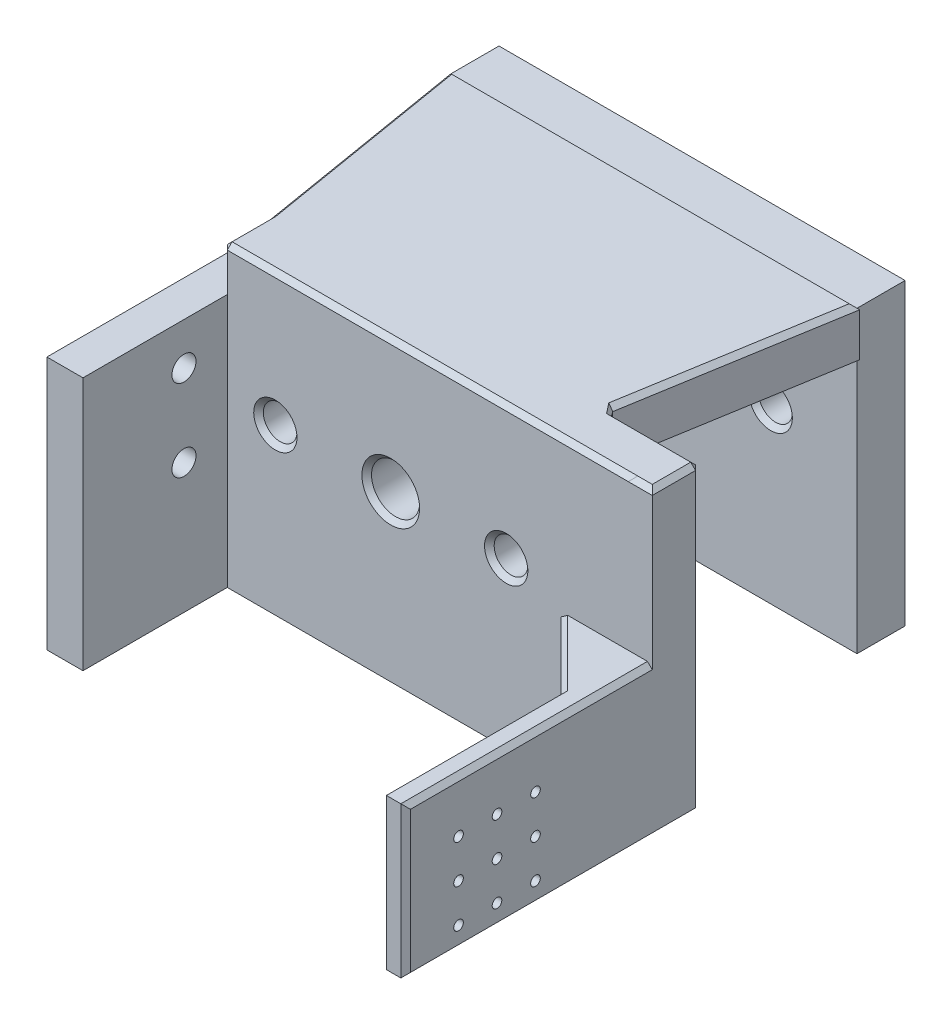
SolidWorks part; units mm, degrees
ref_plane "Front" through (0, 0, 0) normal (0, 0, 1) x (1, 0, 0)
ref_plane "Top" through (0, 0, 0) normal (0, 1, 0) x (1, 0, 0)
ref_plane "Right" through (0, 0, 0) normal (1, 0, 0) x (0, 0, -1)
sketch "Sketch1" plane through (0, 0, 0) normal (0, 0, 1) x (1, 0, 0)
  line L1 (0, 0) -> (70, 0)
  line L2 (0, 0) -> (0, 62.75)
  line L3 (0, 62.75) -> (70, 62.75)
  line L4 (70, 0) -> (70, 62.75)
  dimension "D1" = 70
  dimension "D2" = 62.75
extrude "Boss-Extrude1" add sketch "Sketch1" along normal blind 10
sketch "Sketch2" plane through (0, 0, 10) normal (0, 0, 1) x (1, 0, 0)
  line L1 (70, 62.75) -> (0, 62.75) construction
  line L2 (70, 0) -> (70, 62.75) construction
  circle A0 centre (35, 35.25) radius 5
  dimension "D1" = 27.5
  dimension "D3" = 10
  dimension "D2" = 35
extrude "Cut-Extrude1" cut sketch "Sketch2" against normal through all
sketch "Sketch3" plane through (0, 0, 10) normal (0, 0, 1) x (1, 0, 0)
  line L1 (35, 35.25) -> (92.1007, 35.25) construction
  circle A0 centre (11, 35.25) radius 3.5
  circle A1 centre (59, 35.25) radius 3.5
  circle A2 centre (35, 35.25) radius 5 construction
  dimension "D1" = 7
  dimension "D2" = 7
  dimension "D4" = 48
  dimension "D5" = 24
extrude "Cut-Extrude2" cut sketch "Sketch3" against normal through all
sketch "Sketch4" plane through (0, 62.75, 0) normal (0, 1, 0) x (1, 0, 0)
  line L0 (0, 0) -> (-7.5, 45)
  line L1 (-7.5, 45) -> (77.5, 45)
  line L2 (77.5, 45) -> (70, 0)
  line L3 (70, 0) -> (0, 0)
  line L4 (35, 0) -> (35, 91.9933) construction
  dimension "D1" = 45
  dimension "D2" = 42.5
  dimension "D3" = 42.5
extrude "Boss-Extrude2" add sketch "Sketch4" against normal blind 10
sketch "Sketch5" plane through (0, 0, -45) normal (0, 0, -1) x (-1, 0, 0)
  line L0 (-77.5, 52.75) -> (7.5, 52.75) construction
  line L1 (-52.5, 52.75) -> (-17.5, 52.75)
  line L2 (-52.5, 52.75) -> (-52.5, 59.25)
  line L3 (-52.5, 59.25) -> (-17.5, 59.25)
  line L4 (-17.5, 52.75) -> (-17.5, 59.25)
  line L5 (-77.5, 62.75) -> (7.5, 62.75) construction
  line L6 (7.5, 52.75) -> (7.5, 62.75) construction
  dimension "D1" = 35
  dimension "D2" = 25
  dimension "D3" = 3.5
extrude "Cut-Extrude3" cut sketch "Sketch5" against normal up to surface (45 mm away) up to face at (14.5, 35.25, 0)
chamfer "Chamfer1" distance 1 angle 45 6 edges at (14.5, 35.25, 10) (14.5, 35.25, 0) (62.5, 35.25, 10) (62.5, 35.25, 0) (40, 35.25, 10) (40, 35.25, 0)
chamfer "Chamfer2" distance 6 angle 45 2 edges at (17.5, 52.75, -22.5) (52.5, 52.75, -22.5)
sketch "Sketch6" plane through (70, 0, 0) normal (1, 0, 0) x (0, 0, -1)
  line L1 (-10, 62.75) -> (0, 62.75)
  line L2 (-10, 62.75) -> (-10, 0)
  line L3 (-10, 0) -> (0, 0)
  line L4 (0, 62.75) -> (0, 0)
extrude "Boss-Extrude3" add sketch "Sketch6" along normal blind 19.37
sketch "Sketch7" plane through (0, 0, 10) normal (0, 0, 1) x (1, 0, 0)
  line L0 (89.37, 62.75) -> (0, 62.75) construction
  line L1 (84.37, 62.75) -> (89.37, 62.75)
  line L2 (84.37, 62.75) -> (84.37, 0)
  line L3 (84.37, 0) -> (89.37, 0)
  line L4 (89.37, 62.75) -> (89.37, 0)
  line L5 (0, 0) -> (89.37, 0) construction
  line L6 (89.37, 62.75) -> (89.37, 0) construction
  dimension "D1" = 5
extrude "Boss-Extrude4" add sketch "Sketch7" along normal blind 51.28
sketch "Sketch8" plane through (89.37, 0, 0) normal (1, 0, 0) x (0, 0, -1)
  line L0 (-61.28, 0) -> (-61.28, 62.75) construction
  line L1 (-61.28, 0) -> (0, 0) construction
  line L2 (-61.28, 20.5) -> (0, 20.5) construction
  line L3 (0, 0) -> (0, 62.75) construction
  line L4 (-50.28, 33.1269) -> (-50.28, -8.1623) construction
  circle A0 centre (-50.28, 20.5) radius 1
  circle A1 centre (-42.28, 20.5) radius 1
  circle A2 centre (-34.28, 20.5) radius 1
  circle A3 centre (-42.28, 20.5) radius 1
  circle A4 centre (-34.28, 20.5) radius 1
  circle A5 centre (-42.28, 12.5) radius 1
  circle A6 centre (-34.28, 12.5) radius 1
  circle A7 centre (-42.28, 4.5) radius 1
  circle A8 centre (-34.28, 4.5) radius 1
  circle A9 centre (-50.28, 12.5) radius 1
  circle A10 centre (-50.28, 4.5) radius 1
  dimension "D1" = 2
  dimension "D5" = 8
  dimension "D6" = 3
  dimension "D2" = 11
  dimension "D3" = 20.5
  dimension "D7" = 3
  dimension "D8" = 8
  dimension "D9" = 16
  dimension "D4" = 3
extrude "Cut-Extrude4" cut sketch "Sketch8" against normal up to next contours A2 | A1 | A9 | A5 | A6 | A8 | A7 | A0 | A10 region at (89.37, 20.5, 42.28) region at (89.37, 20.5, 34.28) region at (89.37, 12.5, 42.28) region at (89.37, 12.5, 34.28) region at (89.37, 4.5, 42.28) region at (89.37, 4.5, 34.28) region at (89.37, 12.5, 50.28)
chamfer "Chamfer3" distance 1 angle 45 16 edges at (70, 57.75, 0) (0, 26.375, 0) (89.37, 31.375, 0) (89.37, 31.375, 61.28) (89.37, 62.75, 30.64) (79.685, 62.75, 0) (73.75, 62.75, -22.5) (35, 62.75, -45) (-3.75, 62.75, -22.5) (0, 62.75, 5) (84.37, 31.375, 61.28) (84.37, 0, 35.64) (84.37, 62.75, 35.64) (42.185, 62.75, 10) (42.185, 0, 10) (0, 31.375, 10) first distance on face at (73.75, 57.75, -22.5) first distance on face at (0, 35.65, 4) first distance on face at (89.37, 12.5, 33.28) first distance on face at (54.1644, 62.75, 5.84) first distance on face at (35, 57.25, -45) first distance on face at (-3.75, 57.75, -22.5) first distance on face at (84.37, 12.5, 33.28) first distance on face at (57.9133, 0, 23.76)
sketch "Sketch9" plane through (84.37, 0, 0) normal (-1, 0, 0) x (0, 0, 1)
  line L0 (10, 61.75) -> (10, 1) construction
  line L1 (61.28, 62.75) -> (10, 62.75)
  line L2 (61.28, 62.75) -> (61.28, 31.375)
  line L3 (61.28, 31.375) -> (10, 31.375)
  line L4 (10, 62.75) -> (10, 31.375)
extrude "Cut-Extrude5" cut sketch "Sketch9" against normal up to next
chamfer "Chamfer4" distance 1 angle 45 1 edges at (86.87, 62.75, 10)
chamfer "Chamfer5" distance 1 angle 45 2 edges at (84.37, 31.375, 35.14) (89.37, 31.375, 35.14)
sketch "Sketch11" plane through (0, 0, 0) normal (0, 0, -1) x (-1, 0, 0)
  line L0 (-1, 0) -> (-88.37, 0) construction
  line L1 (-81.87, 3) -> (-76.87, 3)
  line L2 (-81.87, 3) -> (-81.87, 23)
  line L3 (-81.87, 23) -> (-76.87, 23)
  line L4 (-76.87, 3) -> (-76.87, 23)
  line L5 (-88.37, 61.75) -> (-88.37, 0) construction
  line L7 (-88.37, 3) -> (-46.6895, 3) construction
  dimension "D1" = 6.5
  dimension "D2" = 20
  dimension "D3" = 5
  dimension "D4" = 3
extrude "Cut-Extrude6" cut sketch "Sketch11" against normal blind 10
sketch "Sketch12" plane through (0, 31.375, 0) normal (0, 1, 0) x (1, 0, 0)
  line L0 (85.37, -25) -> (70.37, -10)
  line L1 (85.37, -10) -> (85.37, -61.28) construction
  line L2 (84.37, -10) -> (1, -10) construction
  line L3 (70.37, -10) -> (85.37, -10)
  line L4 (85.37, -10) -> (85.37, -25)
  dimension "D1" = 45
  dimension "D2" = 15
extrude "Boss-Extrude5" add sketch "Sketch12" against normal blind 5
sketch "Sketch13" plane through (0, 0, 0) normal (0, -1, 0) x (1, 0, 0)
  line L0 (85.37, 24) -> (70.37, 9)
  line L1 (70.37, 9) -> (85.37, 9)
  line L2 (85.37, 9) -> (85.37, 24)
  line L6 (85.37, 61.28) -> (85.37, 9) construction
  line L9 (85.37, 9) -> (0, 9) construction
  dimension "D1" = 15
  dimension "D2" = 45
extrude "Boss-Extrude6" add sketch "Sketch13" against normal blind 3
chamfer "Chamfer6" distance 1 angle 45 5 edges at (89.37, 0, 30.64) (77.87, 0, 16.5) (77.87, 3, 16.5) (77.37, 26.375, 17) (77.87, 31.375, 17.5)
sketch "Sketch14" plane through (0, 0, 0) normal (-1, 0, 0) x (0, 0, 1)
  line L0 (9, 0) -> (9, 61.75) construction
  line L1 (9, 52.75) -> (-65, 52.75)
  line L2 (9, 52.75) -> (9, 0)
  line L3 (9, 0) -> (-65, 0)
  line L4 (-65, 52.75) -> (-65, 0)
  line L5 (-44, 62.75) -> (-0.0828, 62.75) construction
  dimension "D1" = 74
  dimension "D2" = 52.75
  dimension "D3" = 10
extrude "Boss-Extrude7" add sketch "Sketch14" along normal blind 7.5 and the other way blind 3
sketch "Sketch16" plane through (0, 0, -45) normal (0, 0, -1) x (-1, 0, 0)
  line L1 (7.5, 61.75) -> (-76.9401, 61.75)
  line L2 (7.5, 61.75) -> (7.5, -0.466)
  line L3 (7.5, -0.466) -> (-76.9401, -0.466)
  line L4 (-76.9401, 61.75) -> (-76.9401, -0.466)
extrude "Boss-Extrude8" add sketch "Sketch16" along normal blind 10
sketch "Sketch17" plane through (0, 0, -55) normal (0, 0, -1) x (-1, 0, 0)
  circle A0 centre (-11, 35.25) radius 3.5 construction
  circle A1 centre (-35, 35.25) radius 5 construction
  circle A2 centre (-59, 35.25) radius 3.5 construction
  circle A3 centre (-11, 35.25) radius 3.5
  circle A4 centre (-35, 35.25) radius 5
  circle A5 centre (-59, 35.25) radius 3.5
extrude "Cut-Extrude8" cut sketch "Sketch17" against normal up to next
chamfer "Chamfer7" distance 1 angle 45 6 edges at (7.5, 35.25, -55) (14.5, 35.25, -45) (30, 35.25, -55) (40, 35.25, -45) (55.5, 35.25, -55) (62.5, 35.25, -45)
sketch "Sketch18" plane through (0, 0, 9) normal (0, 0, 1) x (1, 0, 0)
  line L1 (-7.5, 52.75) -> (0, 52.75)
  line L2 (-7.5, 52.75) -> (-7.5, 0)
  line L3 (-7.5, 0) -> (0, 0)
  line L4 (0, 52.75) -> (0, 0)
extrude "Boss-Extrude11" add sketch "Sketch18" along normal blind 30
sketch "Sketch19" plane through (0, 0, -65) normal (0, 0, -1) x (-1, 0, 0)
  line L1 (-3, 52.75) -> (7.5, 52.75)
  line L2 (-3, 52.75) -> (-3, 0)
  line L3 (-3, 0) -> (7.5, 0)
  line L4 (7.5, 52.75) -> (7.5, 0)
extrude "Cut-Extrude9" cut sketch "Sketch19" against normal up to surface (10 mm away) up to face at (15.5, 35.25, -55)
sketch "Sketch20" plane through (3, 0, 0) normal (1, 0, 0) x (0, 0, -1)
  line L0 (0, 52.75) -> (0, 0) construction
  line L1 (0, 52.75) -> (45, 52.75) construction
  line L2 (45, 52.75) -> (45, 0) construction
  circle A0 centre (10, 44) radius 2.5
  circle A1 centre (-18, 44) radius 2.5
  circle A2 centre (-18, 27) radius 2.5
  circle A3 centre (10, 27) radius 2.5
  dimension "D1" = 5
  dimension "D2" = 10
  dimension "D3" = 8.75
  dimension "D6" = 28
  dimension "D7" = 17
  dimension "D8" = 35
  dimension "D4" = 2
  dimension "D5" = 2
extrude "Cut-Extrude10" cut sketch "Sketch20" against normal up to next
